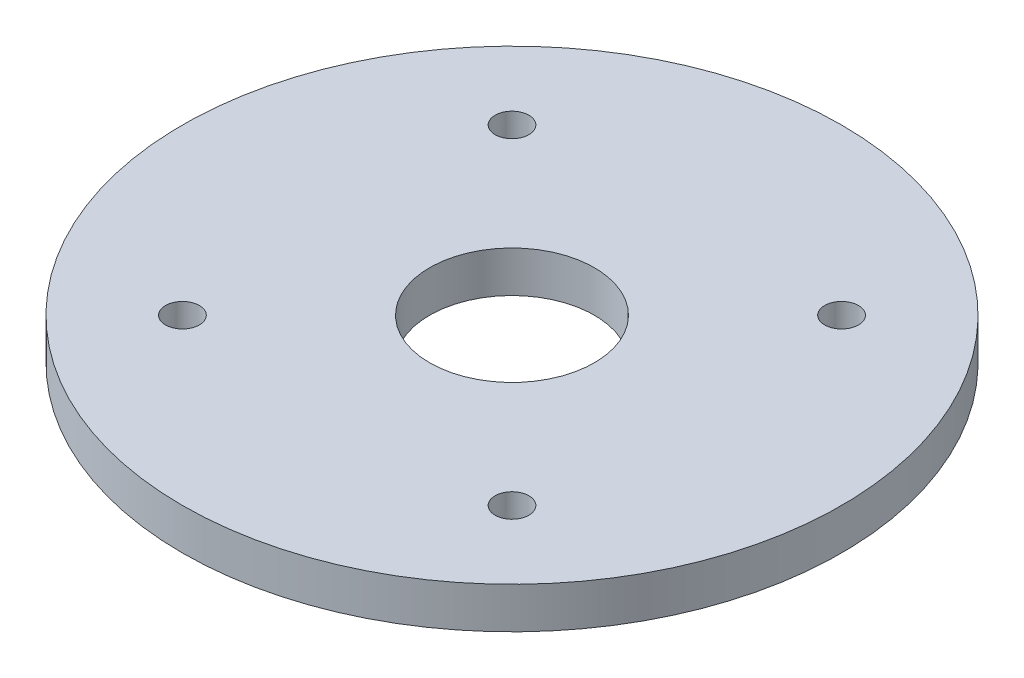
SolidWorks part; units mm, degrees
ref_plane "Спереди" through (0, 0, 0) normal (0, 0, 1) x (1, 0, 0)
ref_plane "Сверху" through (0, 0, 0) normal (0, 1, 0) x (1, 0, 0)
ref_plane "Справа" through (0, 0, 0) normal (1, 0, 0) x (0, 0, -1)
sketch "Эскиз1" plane through (0, 0, 0) normal (0, 1, 0) x (1, 0, 0)
  circle A0 centre (0, 0) radius 20
  circle A1 centre (0, 0) radius 5
  dimension "D1" = 10
  dimension "D2" = 40
extrude "Бобышка-Вытянуть1" add sketch "Эскиз1" along normal blind 2.5
sketch "Эскиз2" plane through (0, 2.5, 0) normal (0, 1, 0) x (1, 0, 0)
  line L0 (-10, 10) -> (10, 10) construction
  line L1 (10, 10) -> (10, -10) construction
  line L2 (10, -10) -> (-10, -10) construction
  line L3 (-10, -10) -> (-10, 10) construction
  line L4 (0, -16.4418) -> (0, 18.5013) construction
  line L5 (-18.2963, 0) -> (19.5347, 0) construction
  point P0 (-10, 10)
  point P1 (10, 10)
  point P2 (10, -10)
  point P3 (-10, -10)
  point P11 (0, 10)
  point P14 (-10, 0)
  dimension "D1" = 20
hole_wizard "Отверстие обработанное метчиком M2.51" positions "Эскиз3" profile "Эскиз4" tap size "M2.5" standard "ISO" end condition through all
sketch "Эскиз3" plane through (0, 2.5, 0) normal (0, 1, 0) x (1, 0, 0)
  point P0 (-10, 10)
  point P3 (10, 10)
  point P6 (10, -10)
  point P9 (-10, -10)
sketch "Эскиз4" plane through (-10, 2.5, -10) normal (1, 0, 0) x (0, 0, 1)
  line L0 (0, 0) -> (0, 2.5)
  line L1 (0, 2.5) -> (1.025, 2.5)
  line L2 (1.025, 2.5) -> (1.025, 0)
  line L5 (1.025, 0) -> (0, 0)
  line L11 (0, -6.35) -> (0, 107.95) construction
  dimension "Диаметр проходного сверла" = 2.05
  dimension "Глубина проходного сверла" = 2.5
cosmetic thread "Отверстие резьбы1" parameters "D2"=2.5
cosmetic thread "Отверстие резьбы2" parameters "D2"=2.5
cosmetic thread "Отверстие резьбы3" parameters "D2"=2.5
cosmetic thread "Отверстие резьбы4" parameters "D2"=2.5
